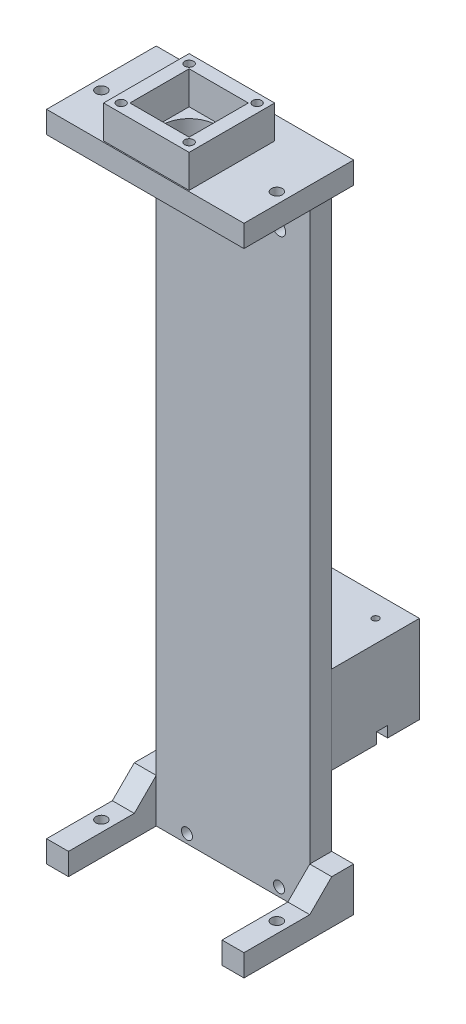
SolidWorks part; units mm, degrees
ref_plane "前视基准面" through (0, 0, 0) normal (0, 0, 1) x (1, 0, 0)
ref_plane "上视基准面" through (0, 0, 0) normal (0, 1, 0) x (1, 0, 0)
ref_plane "右视基准面" through (0, 0, 0) normal (1, 0, 0) x (0, 0, -1)
other "Configuration Table"
sketch "草图1" plane through (0, 0, 0) normal (0, 1, 0) x (1, 0, 0)
  line L1 (-32.1359, 17.2849) -> (37.8641, 17.2849)
  line L2 (-32.1359, 17.2849) -> (-32.1359, -22.7151)
  line L3 (-32.1359, -22.7151) -> (37.8641, -22.7151)
  line L4 (37.8641, 17.2849) -> (37.8641, -22.7151)
  dimension "D1" = 70
  dimension "D2" = 40
extrude "凸台-拉伸1" add sketch "草图1" along normal blind 40
sketch "草图2" plane through (0, 0, 0) normal (0, -1, 0) x (1, 0, 0)
  line L0 (-33.606, 17.7151) -> (40.5423, 17.7151) construction
  line L1 (-32.1359, 22.7151) -> (37.8641, 22.7151) construction
  line L2 (2.8641, 22.7151) -> (2.8641, -17.2849) construction
  line L3 (37.8641, -17.2849) -> (-32.1359, -17.2849) construction
  line L5 (-41.0082, -7.2849) -> (62.2571, -7.2849) construction
  circle A0 centre (-22.1359, 17.7151) radius 1.5
  circle A1 centre (27.8641, 17.7151) radius 1.5
  circle A2 centre (-22.1359, -7.2849) radius 1.5
  circle A3 centre (27.8641, -7.2849) radius 1.5
  dimension "D2" = 25
  dimension "D4" = 25
  dimension "D1" = 5
  dimension "D3" = 10
extrude "切除-拉伸1" cut sketch "草图2" against normal through all
sketch "草图4" plane through (0, 0, 0) normal (0, -1, 0) x (1, 0, 0)
  line L0 (-32.1359, 22.7151) -> (-32.1359, 32.7151)
  line L1 (-32.1359, 32.7151) -> (37.8641, 32.7151)
  line L2 (37.8641, 32.7151) -> (37.8641, 22.7151)
  line L3 (37.8641, 22.7151) -> (-32.1359, 22.7151)
  dimension "D1" = 10
extrude "凸台-拉伸2" add sketch "草图4" along normal blind 52 and the other way blind 236 separate body contours L3 L0 L1 L2
sketch "草图5" plane through (0, 0, 32.7151) normal (0, 0, 1) x (1, 0, 0)
  line L0 (-38.373, -48) -> (39.7493, -48) construction
  line L1 (-32.1359, -52) -> (37.8641, -52) construction
  line L2 (2.8641, 0) -> (2.8641, -52) construction
  line L3 (-32.1359, 0) -> (37.8641, 0) construction
  circle A0 centre (-18.1359, -48) radius 2.5
  circle A1 centre (23.8641, -48) radius 2.5
  dimension "D2" = 21
  dimension "D1" = 4
extrude "切除-拉伸2" cut sketch "草图5" against normal blind 10
sketch "草图6" plane through (0, 0, 32.7151) normal (0, 0, 1) x (1, 0, 0)
  line L0 (-39.8379, 212) -> (51.2489, 212) construction
  line L1 (-32.1359, 236) -> (37.8641, 236) construction
  line L2 (2.8641, 236) -> (2.8641, 203.179) construction
  circle A0 centre (-18.1359, 212) radius 3
  circle A1 centre (23.8641, 212) radius 3
  dimension "D2" = 21
  dimension "D1" = 24
extrude "切除-拉伸3" cut sketch "草图6" against normal blind 10
sketch "草图7" plane through (0, 0, 22.7151) normal (0, 0, -1) x (-1, 0, 0)
  line L0 (-37.8641, 236) -> (-37.8641, 246)
  line L1 (-37.8641, 246) -> (32.1359, 246)
  line L2 (32.1359, 246) -> (32.1359, 236)
  line L3 (32.1359, 236) -> (-37.8641, 236)
  dimension "D1" = 10
extrude "凸台-拉伸3" add sketch "草图7" against normal blind 50
sketch "草图8" plane through (0, 236, 0) normal (0, -1, 0) x (1, 0, 0)
  line L0 (-32.1359, 72.7151) -> (37.8641, 32.7151) construction
  line L1 (37.8641, 72.7151) -> (-32.1359, 32.7151) construction
  circle A0 centre (2.8641, 52.7151) radius 12.5
extrude "切除-拉伸4" cut sketch "草图8" against normal blind 10
sketch "草图12" plane through (0, 246, 0) normal (0, 1, 0) x (1, 0, 0)
  line L0 (2.8641, -52.7151) -> (49.57, -52.7151) construction
  line L1 (2.8641, -52.7151) -> (-42.4096, -52.7151) construction
  line L2 (2.8641, -22.7151) -> (2.8641, -78.6614) construction
  line L3 (-32.1359, -22.7151) -> (37.8641, -22.7151) construction
  line L4 (-14.6359, -35.2151) -> (-14.6359, -70.2151) construction
  line L5 (-16.6359, -33.2151) -> (22.3641, -33.2151)
  line L6 (-16.6359, -33.2151) -> (-16.6359, -72.2151)
  line L7 (-16.6359, -72.2151) -> (22.3641, -72.2151)
  line L8 (22.3641, -33.2151) -> (22.3641, -72.2151)
  line L9 (-14.6359, -70.2151) -> (20.3641, -70.2151) construction
  line L10 (20.3641, -35.2151) -> (20.3641, -70.2151) construction
  line L11 (-14.6359, -35.2151) -> (20.3641, -35.2151) construction
  dimension "D1" = 39
  dimension "D2" = 39
  dimension "D3" = 19.5
  dimension "D5" = 19.5
  dimension "D4" = 2
extrude "拉伸-薄壁2" add sketch "草图12" along normal blind 15 thin thin type one direction reverse wall 6
sketch "草图14" plane through (0, 261, 0) normal (0, 1, 0) x (1, 0, 0)
  line L0 (-16.6359, -52.7151) -> (22.3641, -52.7151) construction
  line L1 (-16.6359, -33.2151) -> (-16.6359, -72.2151) construction
  line L2 (22.3641, -72.2151) -> (22.3641, -33.2151) construction
  line L3 (2.8641, -33.2151) -> (2.8641, -72.2151) construction
  line L4 (22.3641, -33.2151) -> (-16.6359, -33.2151) construction
  line L5 (-16.6359, -72.2151) -> (22.3641, -72.2151) construction
  circle A0 centre (-12.6359, -37.2151) radius 2
  circle A1 centre (18.3641, -37.2151) radius 2
  circle A2 centre (-12.6359, -68.2151) radius 2
  circle A3 centre (18.3641, -68.2151) radius 2
  dimension "D1" = 15.5
  dimension "D2" = 15.5
extrude "切除-拉伸5" cut sketch "草图14" against normal blind 25
sketch "草图15" plane through (0, 0, 0) normal (0, -1, 0) x (1, 0, 0)
  line L0 (-32.1359, -0.2849) -> (37.8641, -0.2849) construction
  line L1 (-32.1359, -17.2849) -> (-32.1359, 22.7151) construction
  line L2 (37.8641, 22.7151) -> (37.8641, -17.2849) construction
  line L3 (-32.1359, 2.2151) -> (37.8641, 2.2151)
  line L4 (37.8641, 2.2151) -> (37.8641, -2.7849)
  line L5 (37.8641, -2.7849) -> (-32.1359, -2.7849)
  line L6 (-32.1359, -2.7849) -> (-32.1359, 2.2151)
  circle A0 centre (-22.1359, -7.2849) radius 1.5 construction
  dimension "D1" = 7
  dimension "D2" = 5
  dimension "D3" = 2.5
extrude "切除-拉伸6" cut sketch "草图15" against normal blind 5
sketch "草图16" plane through (-32.1359, 0, 0) normal (-1, 0, 0) x (0, 0, 1)
  line L0 (22.7151, 246) -> (72.7151, 246)
  line L1 (72.7151, 246) -> (72.7151, 236)
  line L2 (72.7151, 236) -> (22.7151, 236)
  line L3 (22.7151, 246) -> (22.7151, -52) construction
  line L4 (22.7151, 236) -> (22.7151, 246)
extrude "凸台-拉伸5" add sketch "草图16" along normal blind 10
ref_plane "基准面3" through (0, 97, 0) normal (0, 1, 0) x (1, 0, 0)
mirror "镜向1" about plane through (0, 97, 0) normal (0, 1, 0) of "凸台-拉伸5"
ref_plane "基准面4" through (2.8641, 0, 0) normal (-1, 0, 0) x (0, 0, 1)
mirror "镜向2" about plane through (2.8641, 0, 0) normal (-1, 0, 0) of "镜向1", "凸台-拉伸5"
sketch "草图17" plane through (0, -52, 0) normal (0, -1, 0) x (1, 0, 0)
  line L0 (-32.1359, 52.7151) -> (37.8641, 52.7151) construction
  line L1 (-32.1359, 72.7151) -> (-32.1359, 32.7151) construction
  line L2 (37.8641, 72.7151) -> (37.8641, 32.7151) construction
  line L3 (2.8641, 72.7151) -> (2.8641, 32.7151) construction
  line L4 (47.8641, 72.7151) -> (-42.1359, 72.7151) construction
  line L5 (-32.1359, 32.7151) -> (37.8641, 32.7151) construction
  circle A0 centre (-37.1359, 52.7151) radius 2.5
  circle A1 centre (42.8641, 52.7151) radius 2.5
  dimension "D1" = 5
extrude "切除-拉伸7" cut sketch "草图17" against normal through all
sketch "草图18" plane through (0, -52, 0) normal (0, -1, 0) x (1, 0, 0)
  circle A0 centre (-37.1359, 52.7151) radius 2.5
  circle A1 centre (42.8641, 52.7151) radius 2.5
extrude "凸台-拉伸6" add sketch "草图18" against normal blind 5
sketch "草图21" plane through (0, 0, 22.7151) normal (0, 0, -1) x (-1, 0, 0)
  line L1 (-37.8641, 236) -> (-37.8641, -42) construction
  line L2 (-37.8641, -32) -> (-37.8641, -42)
  line L3 (-37.8641, -42) -> (-47.8641, -42)
  line L4 (-37.8641, -32) -> (-47.8641, -32)
  line L5 (-47.8641, -32) -> (-47.8641, -42)
  dimension "D1" = 10
extrude "凸台-拉伸8" add sketch "草图21" against normal up to surface (10 mm away) up to face at (-15.1359, 212, 32.7151)
mirror "镜向3" about plane through (2.8641, 0, 0) normal (-1, 0, 0) of "凸台-拉伸8"
sketch "草图22" plane through (47.8641, 0, 0) normal (1, 0, 0) x (0, 0, -1)
  line L0 (-32.7151, -32) -> (-42.7151, -42)
  line L1 (-32.7151, -42) -> (-72.7151, -42) construction
  line L2 (-42.7151, -42) -> (-32.7151, -42)
  line L3 (-32.7151, -42) -> (-32.7151, -32)
  dimension "D1" = 10
extrude "凸台-拉伸9" add sketch "草图22" against normal up to surface (10 mm away) up to face at (37.8641, 102, 27.7151)
sketch "草图23" plane through (-42.1359, 0, 0) normal (-1, 0, 0) x (0, 0, 1)
  line L0 (32.7151, -32) -> (42.7151, -42)
  line L1 (42.7151, -42) -> (32.7151, -42)
  line L2 (32.7151, -52) -> (32.7151, -32) construction
  line L3 (32.7151, -42) -> (32.7151, -32)
extrude "凸台-拉伸10" add sketch "草图23" against normal up to surface (10 mm away) contours L3 L0 L1 up to face at (-32.1359, -47, 52.7151)
